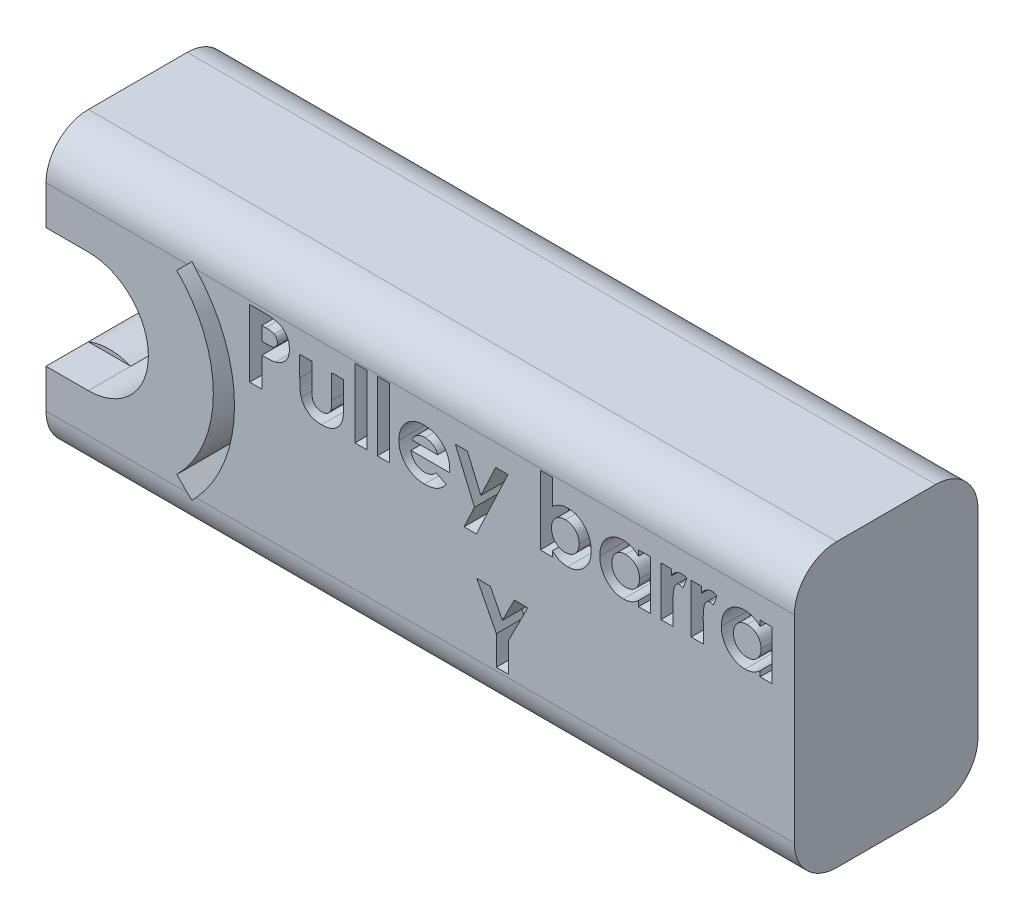
SolidWorks part; units mm, degrees
ref_plane "Front Plane" through (0, 0, 0) normal (0, 0, 1) x (1, 0, 0)
ref_plane "Top Plane" through (0, 0, 0) normal (0, 1, 0) x (1, 0, 0)
ref_plane "Right Plane" through (0, 0, 0) normal (1, 0, 0) x (0, 0, -1)
sketch "Croquis1" plane through (0, 0, 0) normal (0, 0, 1) x (1, 0, 0)
  line L0 (0, 0) -> (0, 20)
  line L1 (0, 20) -> (-50, 20)
  line L2 (-50, 20) -> (-50, 14.25)
  line L3 (0, 0) -> (-50, 0)
  line L4 (-50, 0) -> (-50, 5.75)
  line L5 (0, 10) -> (-50, 10) construction
  line L6 (-50, 14.25) -> (-50, 5.75) construction
  arc A0 (-50, 14.25) -> (-50, 5.75) centre (-50, 10) cw
  dimension "D2" = 4.25
  dimension "D1" = 50
  dimension "D3" = 20
extrude "Saliente-Extruir1" add sketch "Croquis1" along normal blind 13
sketch "Croquis2" plane through (0, 0, 0) normal (0, 0, -1) x (-1, 0, 0)
  line L0 (50, 4.75) -> (50, 2.75)
  line L1 (50, 15.25) -> (50, 17.25)
  line L2 (50, 5.75) -> (50, 0) construction
  line L4 (50, 20) -> (50, 14.25) construction
  arc A1 (50, 17.25) -> (50, 2.75) centre (50, 10) ccw
  arc A2 (50, 15.25) -> (50, 4.75) centre (50, 10) ccw
  arc A3 (50, 14.25) -> (50, 5.75) centre (50, 10) ccw construction
  dimension "D2" = 5.25
  dimension "D1" = 2
extrude "Saliente-Extruir2" [suppressed] add sketch "Croquis2" along normal blind 4
sketch "Croquis3" plane through (0, 0, 13) normal (0, 0, 1) x (1, 0, 0)
  line L0 (-50, 10) -> (-42.6814, 17.3186)
  line L1 (-50, 10) -> (-42.6814, 2.6814)
  line L2 (-50, 5.75) -> (-50, 0) construction
  circle A0 centre (-50, 10) radius 10.35
  circle A1 centre (-50, 10) radius 8.85
  dimension "D1" = 17.7
  dimension "D2" = 20.7
  dimension "D3" = 90
  dimension "D4" = 45
extrude "Cortar-Extruir1" cut sketch "Croquis3" against normal blind 5 contours A1 L1 A0 L0 region at (-43.1043, 16.6808, 13)
sketch "Croquis4" plane through (0, 0, 13) normal (0, 0, 1) x (1, 0, 0)
  text T0 "<b>Pulley barra </b>\r\n<b>         Y</b>" font "Century Gothic" height in points 18
extrude "Cortar-Extruir2" cut sketch "Croquis4" against normal blind 2
sketch "Croquis6" plane through (-50, 0, 0) normal (-1, 0, 0) x (0, 0, 1)
  line L8 (0, 20) -> (0, 14.25)
  line L13 (0, 14.25) -> (13, 14.25)
  line L14 (13, 14.25) -> (13, 20)
  line L15 (13, 20) -> (0, 20)
  line L16 (0, 20) -> (0, 14.25)
  line L21 (0, 14.25) -> (13, 14.25)
  line L22 (13, 14.25) -> (13, 20)
  line L23 (13, 20) -> (0, 20)
  line L24 (0, 5.75) -> (0, 0)
  line L29 (0, 0) -> (13, 0)
  line L30 (13, 0) -> (13, 5.75)
  line L31 (13, 5.75) -> (0, 5.75)
  line L32 (0, 5.75) -> (0, 0)
  line L37 (0, 0) -> (13, 0)
  line L38 (13, 0) -> (13, 5.75)
  line L39 (13, 5.75) -> (0, 5.75)
  dimension "D1" = 0
  dimension "D2" = 0
extrude "Saliente-Extruir3" add sketch "Croquis6" along normal blind 3
fillet "Redondeo1" radius 3 4 edges at (-26.5, 20, 0) (-26.5, 0, 0) (-26.5, 0, 13) (-26.5, 20, 13)
sketch "Croquis7" plane through (0, 0, 13) normal (0, 0, 1) x (1, 0, 0)
  line L0 (-53, 14.25) -> (-50, 14.25)
  line L1 (-53, 5.75) -> (-50, 5.75)
  arc A0 (-50, 14.25) -> (-53, 14.25) centre (-51.5, 17.9581) cw
  arc A1 (-53, 5.75) -> (-50, 5.75) centre (-51.5, 2.0419) cw
  dimension "D1" = 4
extrude "Saliente-Extruir4" add sketch "Croquis7" against normal offset from surface (7 mm away) 3 from offset 3 up to face at (-38.4688, 10, 0) offset against normal yes
